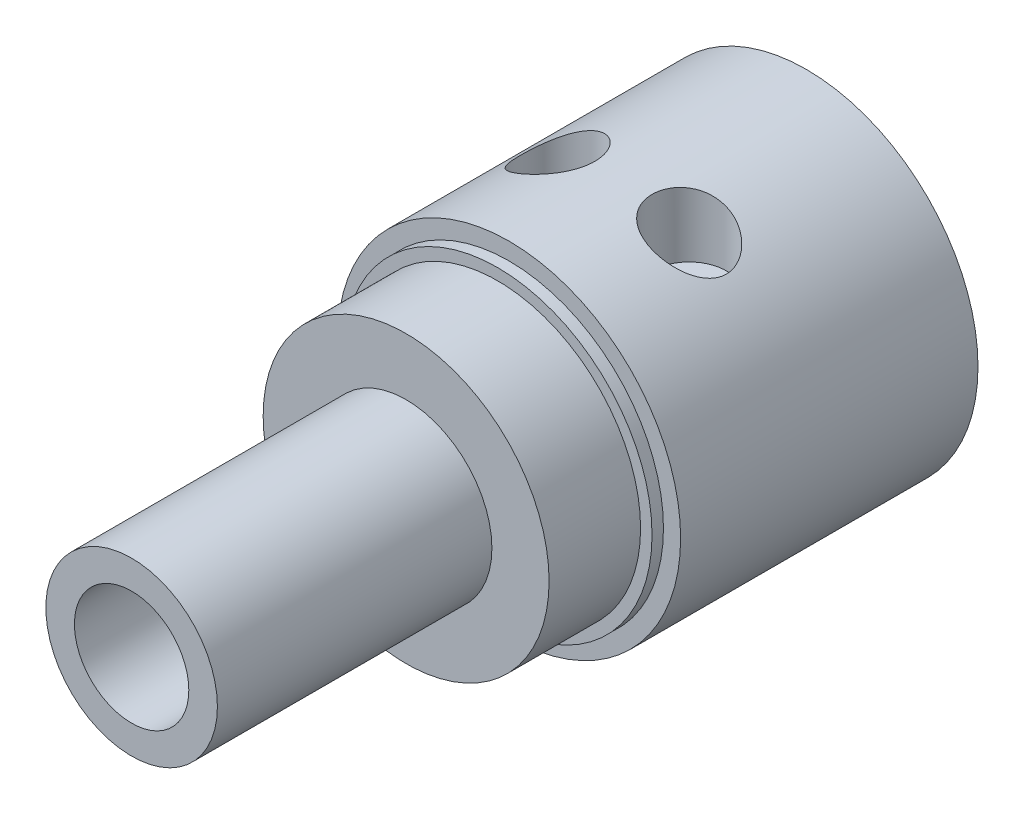
SolidWorks part; units mm, degrees
ref_plane "Front Plane" through (0, 0, 0) normal (0, 0, 1) x (1, 0, 0)
ref_plane "Top Plane" through (0, 0, 0) normal (0, 1, 0) x (1, 0, 0)
ref_plane "Right Plane" through (0, 0, 0) normal (1, 0, 0) x (0, 0, -1)
sketch "Sketch1" plane through (0, 0, 0) normal (0, 0, 1) x (1, 0, 0)
  circle A0 centre (0, 0) radius 15
  dimension "D1" = 30
extrude "Boss-Extrude1" add sketch "Sketch1" along normal blind 35
sketch "Sketch2" plane through (0, 0, 35) normal (0, 0, 1) x (1, 0, 0)
  circle A0 centre (0, 0) radius 13.5
  dimension "D1" = 27
extrude "Cut-Extrude1" cut sketch "Sketch2" against normal blind 9 flip side to cut
sketch "Sketch3" plane through (0, 0, 35) normal (0, 0, 1) x (1, 0, 0)
  circle A0 centre (0, 0) radius 12.5
  dimension "D1" = 25
extrude "Cut-Extrude2" cut sketch "Sketch3" against normal blind 8 flip side to cut
sketch "Sketch4" plane through (0, 0, 0) normal (0, 0, -1) x (-1, 0, 0)
  circle A0 centre (0, 0) radius 8.25
  dimension "D1" = 16.5
extrude "Cut-Extrude3" cut sketch "Sketch4" against normal blind 11
ref_plane "Plane1" through (0, 15, 0) normal (0, 1, 0) x (1, 0, 0)
hole_wizard "CBORE for M3 SHCS1" positions "Sketch6" profile "Sketch5" counterbore size "M3" standard "ANSI Metric" end condition through all
sketch "Sketch6" plane through (0, 15, 0) normal (0, 1, 0) x (1, 0, 0)
  line L0 (-5.75, -16) -> (5.75, -16) construction
  line L3 (15, 0) -> (-15, 0) construction
  point P0 (-5.75, -16)
  point P2 (5.75, -16)
  point P11 (0, -16)
  dimension "D1" = 11.5
  dimension "D2" = 16
sketch "Sketch5" plane through (-5.75, 15, 16) normal (1, 0, 0) x (0, 0, 1)
  line L0 (0, 0) -> (0, 30)
  line L1 (0, 30) -> (1.7, 30)
  line L3 (1.7, 30) -> (1.7, 6)
  line L4 (1.7, 6) -> (3.25, 6)
  line L5 (3.25, 6) -> (3.25, 0)
  line L7 (3.25, 0) -> (0, 0)
  line L11 (0, -6.35) -> (0, 107.95) construction
  dimension "Thru Hole Dia." = 3.4
  dimension "Thru Hole Depth" = 30
  dimension "C'Bore Dia." = 6.5
  dimension "C'Bore Depth" = 6
sketch "Sketch7" plane through (0, 0, 35) normal (0, 0, 1) x (1, 0, 0)
  circle A0 centre (0, 0) radius 7.5
  dimension "D1" = 15
extrude "Boss-Extrude2" add sketch "Sketch7" along normal blind 24
sketch "Sketch8" plane through (0, 0, 59) normal (0, 0, 1) x (1, 0, 0)
  circle A0 centre (0, 0) radius 5
  dimension "D1" = 10
extrude "Cut-Extrude4" cut sketch "Sketch8" against normal through all
